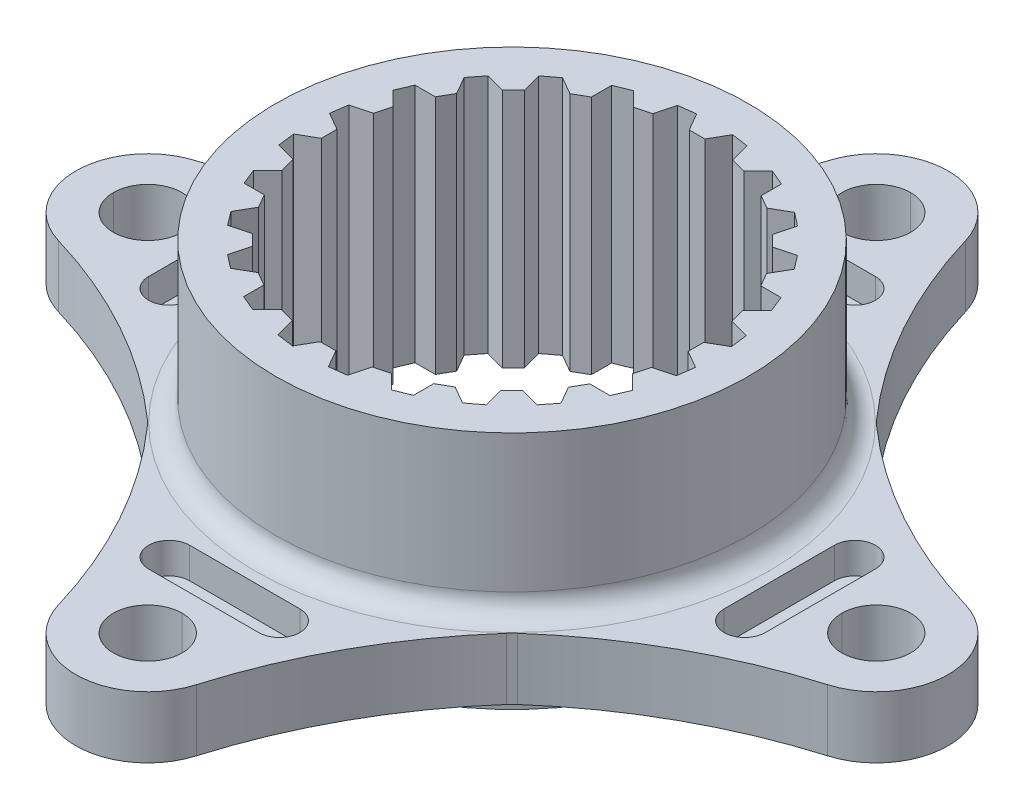
SolidWorks part; units mm, degrees
note: '?' marks a value the reader was unsure of. The reader was unsure of these and kept them because the rebuilt part matched: shared geometry of "Sketch6<5>".
material "7075-T6 (SN)"
ref_plane "Front Plane" through (0, 0, 0) normal (0, 0, 1) x (1, 0, 0)
ref_plane "Top Plane" through (0, 0, 0) normal (0, 1, 0) x (1, 0, 0)
ref_plane "Right Plane" through (0, 0, 0) normal (1, 0, 0) x (0, 0, -1)
sketch "Sketch1" plane through (0, 0, 0) normal (0, 1, 0) x (1, 0, 0)
  line L0 (274.6284, 454.6081) -> (780.6456, 454.6081) construction
  circle A0 centre (0, 0) radius 23
  dimension "D1" = 46
sketch "Sketch5" plane through (0, 0, 0) normal (0, 1, 0) x (1, 0, 0)
  circle A0 centre (0, 0) radius 23
  circle A1 centre (0, 0) radius 25
  dimension "D1" = 46
  dimension "D2" = 50
sketch "Sketch6" plane through (0, 0, 0) normal (0, 1, 0) x (1, 0, 0)
  line L0 (-0.9689, -22.7363) -> (0.9689, -22.7363)
  line L1 (0.9689, -22.7363) -> (2.2189, -24.9013)
  line L2 (0, 33.3652) -> (0, -36.4848) construction
  line L3 (-0.9689, -22.7363) -> (-2.2189, -24.9013)
  line L4 (-4.9456, -22.1943) -> (-4.2985, -24.6091)
  line L5 (-6.8174, -21.6927) -> (-4.9456, -22.1943)
  line L6 (-6.8174, -21.6927) -> (-8.5852, -23.4605)
  line L7 (-10.5182, -22.6399) -> (-8.5852, -23.4605)
  line L8 (-10.5182, -20.1399) -> (-10.5182, -22.6399)
  line L9 (-12.1965, -19.171) -> (-10.5182, -20.1399)
  line L10 (-12.1965, -19.171) -> (-14.3615, -20.421)
  line L11 (-16.0164, -19.1281) -> (-14.3615, -20.421)
  line L12 (-15.3693, -16.7133) -> (-16.0164, -19.1281)
  line L13 (-16.7396, -15.343) -> (-15.3693, -16.7133)
  line L14 (-16.7396, -15.343) -> (-19.1544, -15.99)
  line L15 (-20.4182, -14.3129) -> (-19.1544, -15.99)
  line L16 (-19.1682, -12.1478) -> (-20.4182, -14.3129)
  line L17 (-20.1372, -10.4696) -> (-19.1682, -12.1478)
  line L18 (-20.1372, -10.4696) -> (-22.6372, -10.4696)
  line L19 (-23.4239, -8.5225) -> (-22.6372, -10.4696)
  line L20 (-21.6561, -6.7547) -> (-23.4239, -8.5225)
  line L21 (-22.1576, -4.8829) -> (-21.6561, -6.7547)
  line L22 (-22.1576, -4.8829) -> (-24.5725, -4.2358)
  line L23 (-24.8284, -2.1515) -> (-24.5725, -4.2358)
  line L24 (-22.6633, -0.9015) -> (-24.8284, -2.1515)
  line L25 (-22.6633, 1.0364) -> (-22.6633, -0.9015)
  line L26 (-22.6633, 1.0364) -> (-24.8284, 2.2864)
  line L27 (-24.5361, 4.366) -> (-24.8284, 2.2864)
  line L28 (-22.1213, 5.013) -> (-24.5361, 4.366)
  line L29 (-21.6197, 6.8849) -> (-22.1213, 5.013)
  line L30 (-21.6197, 6.8849) -> (-23.3875, 8.6526)
  line L31 (-22.567, 10.5857) -> (-23.3875, 8.6526)
  line L32 (-20.067, 10.5857) -> (-22.567, 10.5857)
  line L33 (-19.098, 12.2639) -> (-20.067, 10.5857)
  line L34 (-19.098, 12.2639) -> (-20.348, 14.429)
  line L35 (-19.0552, 16.0838) -> (-20.348, 14.429)
  line L36 (-16.6403, 15.4368) -> (-19.0552, 16.0838)
  line L37 (-15.27, 16.8071) -> (-16.6403, 15.4368)
  line L38 (-15.27, 16.8071) -> (-15.9171, 19.2219)
  line L39 (-14.24, 20.4857) -> (-15.9171, 19.2219)
  line L40 (-12.0749, 19.2357) -> (-14.24, 20.4857)
  line L41 (-10.3966, 20.2046) -> (-12.0749, 19.2357)
  line L42 (-10.3966, 20.2046) -> (-10.3966, 22.7046)
  line L43 (-8.4496, 23.4913) -> (-10.3966, 22.7046)
  line L44 (-6.6818, 21.7235) -> (-8.4496, 23.4913)
  line L45 (-4.8099, 22.2251) -> (-6.6818, 21.7235)
  line L46 (-4.8099, 22.2251) -> (-4.1629, 24.6399)
  line L47 (-2.0785, 24.8958) -> (-4.1629, 24.6399)
  line L48 (-0.8285, 22.7308) -> (-2.0785, 24.8958)
  line L49 (1.1093, 22.7308) -> (-0.8285, 22.7308)
  line L50 (1.1093, 22.7308) -> (2.3593, 24.8958)
  line L51 (4.4389, 24.6036) -> (2.3593, 24.8958)
  line L52 (5.086, 22.1888) -> (4.4389, 24.6036)
  line L53 (6.9578, 21.6872) -> (5.086, 22.1888)
  line L54 (6.9578, 21.6872) -> (8.7256, 23.455)
  line L55 (10.6586, 22.6344) -> (8.7256, 23.455)
  line L56 (10.6586, 20.1344) -> (10.6586, 22.6344)
  line L57 (12.3369, 19.1655) -> (10.6586, 20.1344)
  line L58 (12.3369, 19.1655) -> (14.5019, 20.4155)
  line L59 (16.1568, 19.1226) -> (14.5019, 20.4155)
  line L60 (15.5097, 16.7078) -> (16.1568, 19.1226)
  line L61 (16.88, 15.3375) -> (15.5097, 16.7078)
  line L62 (16.88, 15.3375) -> (19.2948, 15.9845)
  line L63 (20.5586, 14.3074) -> (19.2948, 15.9845)
  line L64 (19.3086, 12.1424) -> (20.5586, 14.3074)
  line L65 (20.2776, 10.4641) -> (19.3086, 12.1424)
  line L66 (20.2776, 10.4641) -> (22.7776, 10.4641)
  line L67 (23.5643, 8.517) -> (22.7776, 10.4641)
  line L68 (21.7965, 6.7492) -> (23.5643, 8.517)
  line L69 (22.298, 4.8774) -> (21.7965, 6.7492)
  line L70 (22.298, 4.8774) -> (24.7129, 4.2303)
  line L71 (24.9688, 2.146) -> (24.7129, 4.2303)
  line L72 (22.8037, 0.896) -> (24.9688, 2.146)
  line L73 (22.8037, -1.0419) -> (22.8037, 0.896)
  line L74 (22.8037, -1.0419) -> (24.9688, -2.2919)
  line L75 (24.6765, -4.3714) -> (24.9688, -2.2919)
  line L76 (22.2617, -5.0185) -> (24.6765, -4.3714)
  line L77 (21.7601, -6.8903) -> (22.2617, -5.0185)
  line L78 (21.7601, -6.8903) -> (23.5279, -8.6581)
  line L79 (22.7074, -10.5912) -> (23.5279, -8.6581)
  line L80 (20.2074, -10.5912) -> (22.7074, -10.5912)
  line L81 (19.2384, -12.2694) -> (20.2074, -10.5912)
  line L82 (19.2384, -12.2694) -> (20.4884, -14.4345)
  line L83 (19.1955, -16.0893) -> (20.4884, -14.4345)
  line L84 (16.7807, -15.4423) -> (19.1955, -16.0893)
  line L85 (15.4104, -16.8126) -> (16.7807, -15.4423)
  line L86 (15.4104, -16.8126) -> (16.0575, -19.2274)
  line L87 (14.3804, -20.4912) -> (16.0575, -19.2274)
  line L88 (12.2153, -19.2412) -> (14.3804, -20.4912)
  line L89 (10.537, -20.2101) -> (12.2153, -19.2412)
  line L90 (10.537, -20.2101) -> (10.537, -22.7101)
  line L91 (8.59, -23.4968) -> (10.537, -22.7101)
  line L92 (6.8222, -21.729) -> (8.59, -23.4968)
  line L93 (4.9503, -22.2306) -> (6.8222, -21.729)
  line L94 (4.9503, -22.2306) -> (4.3033, -24.6454)
  line L95 (2.2189, -24.9013) -> (4.3033, -24.6454)
  line L96 (-4.2985, -24.6091) -> (-2.2189, -24.9013)
  circle A0 centre (0, 0) radius 23 construction
  circle A1 centre (0, 0) radius 25 construction
  point P11 (0, -23)
  point P131 (0.0702, -0.0027)
  dimension "D4" = 2.5
  dimension "D1" = 2.1
  dimension "D5" = 112
  dimension "D6" = 120
  dimension "D2" = 1.9379
  dimension "D3" = 24
sketch "Sketch8" plane through (0, 0, 0) normal (0, 1, 0) x (1, 0, 0)
  circle A0 centre (0, 0) radius 100
  dimension "D1" = 200
extrude "Boss-Extrude4" add sketch "Sketch8" along normal blind 27.178 contours A0
extrude "Cut-Extrude1" cut sketch "Sketch6" along normal through all
sketch "Sketch9" plane through (0, 27.178, 0) normal (0, 1, 0) x (1, 0, 0)
  circle A0 centre (0, 0) radius 29.21
  dimension "D1" = 58.42
extrude "Cut-Extrude3" cut sketch "Sketch9" against normal blind 19.558 flip side to cut
sketch "Sketch10" plane through (0, 7.62, 0) normal (0, 1, 0) x (1, 0, 0)
  circle A1 centre (0, 45.0088) radius 4.2545
  circle A4 centre (45.0088, 0) radius 4.2545
  circle A5 centre (0, -45.0088) radius 4.2545
  circle A6 centre (-45.0088, 0) radius 4.2545
  point P11 (0, 0)
  point P28 (0, 0)
  dimension "D1" = 4
  dimension "D2" = 8.509
  dimension "D3" = 45.0088
sketch "Sketch11" plane through (0, 7.62, 0) normal (0, 1, 0) x (1, 0, 0)
  line L0 (0, 45.0088) -> (45.0088, 0) construction
  line L1 (0, 0) -> (70.7107, 70.7107) construction
  line L2 (0, 45.0088) -> (8.89, 45.0088) construction
  line L3 (0, 45.0088) -> (8.5239, 47.5337) construction
  circle A0 centre (0, 0) radius 100 construction
  arc A1 (8.5239, 47.5337) -> (22.5044, 22.5044) centre (71.1084, 66.0721) ccw
  arc A2 (47.5337, 8.5239) -> (22.5044, 22.5044) centre (66.0721, 71.1084) cw
  arc A3 (47.5337, -8.5239) -> (22.5044, -22.5044) centre (66.0721, -71.1084) ccw
  arc A4 (-8.5239, -47.5337) -> (-22.5044, -22.5044) centre (-71.1084, -66.0721) ccw
  arc A5 (-47.5337, 8.5239) -> (-22.5044, 22.5044) centre (-66.0721, 71.1084) ccw
  arc A6 (8.5239, -47.5337) -> (22.5044, -22.5044) centre (71.1084, -66.0721) cw
  arc A7 (-47.5337, -8.5239) -> (-22.5044, -22.5044) centre (-66.0721, -71.1084) cw
  circle A8 centre (0, 45.0088) radius 8.89
  circle A9 centre (45.0088, 0) radius 8.89
  circle A10 centre (0, -45.0088) radius 8.89
  circle A11 centre (-45.0088, 0) radius 8.89
  arc A12 (-8.5239, 47.5337) -> (-22.5044, 22.5044) centre (-71.1084, 66.0721) cw
  point P15 (0, 0)
  point P31 (0, 0)
  point P37 (0, 0)
  point P42 (0, 0)
  point P51 (0, 0)
  dimension "D4" = 4
  dimension "D1" = 4
  dimension "D2" = 17.78
  dimension "D5" = 4
  dimension "D3" = 16.5
extrude "Cut-Extrude6" cut sketch "Sketch11" against normal blind 7.62
extrude "Cut-Extrude7" cut sketch "Sketch10" against normal blind 7.62
fillet "Fillet2" radius 2.54 1 edges at (0, 7.62, 29.21)
ref_plane "Plane1" through (0, 0, 0) normal (0, 0, 1) x (1, 0, 0)
ref_plane "Plane2" through (0, 0, 0) normal (-1, 0, 0) x (0, 0, 1)
split line "Split Line1"
split line "Split Line2"
ref_axis "Axis1" through (0, 8.001, 0) along (0, -1, 0)?
fillet "Fillet3" radius 7.62 4 edges at (-22.5044, 3.81, -22.5044) (22.5044, 3.81, -22.5044) (22.5044, 3.81, 22.5044) (-22.5044, 3.81, 22.5044)
sketch "Sketch13" plane through (0, 7.62, 0) normal (0, 1, 0) x (1, 0, 0)
  line L0 (0, 4.191) -> (0, -4.191) construction
  line L1 (-8.4262, 38.1) -> (8.4262, 38.1)
  line L2 (-8.4262, 38.1) -> (-10.795, 33.02)
  line L3 (-10.795, 33.02) -> (10.795, 33.02)
  line L4 (8.4262, 38.1) -> (10.795, 33.02)
  point P11 (0, 33.02)
  dimension "D1" = 115
  dimension "D2" = 115
  dimension "D3" = 5.08
  dimension "D4" = 0
  dimension "D5" = 21.59
  dimension "D6" = 33.02
extrude "Cut-Extrude12" cut sketch "Sketch13" against normal blind 3.81 contours L1 L4 L3 L2
fillet "Fillet5" radius 2.54 4 edges at (-10.795, 5.715, -33.02) (10.795, 5.715, -33.02) (-8.4262, 5.715, -38.1) (8.4262, 5.715, -38.1)
pattern_circular "CirPattern1" count 4 over 360 about axis through (0, 0, 0) along (0, 1, 0) of "Cut-Extrude12", "Fillet5"
sketch "Sketch14" plane through (0, 0, 0) normal (0, -1, 0) x (1, 0, 0)
  circle A0 centre (0, 0) radius 29.0322
  dimension "D1" = 58.0644
extrude "Boss-Extrude5" add sketch "Sketch14" along normal blind 2.54
extrude "Cut-Extrude17" cut sketch "Sketch6<5>" against normal blind 2.54
sketch "Sketch6<5>" plane through (0, 0, 0) normal (0, 1, 0) x (1, 0, 0) same geometry as "Sketch6"
